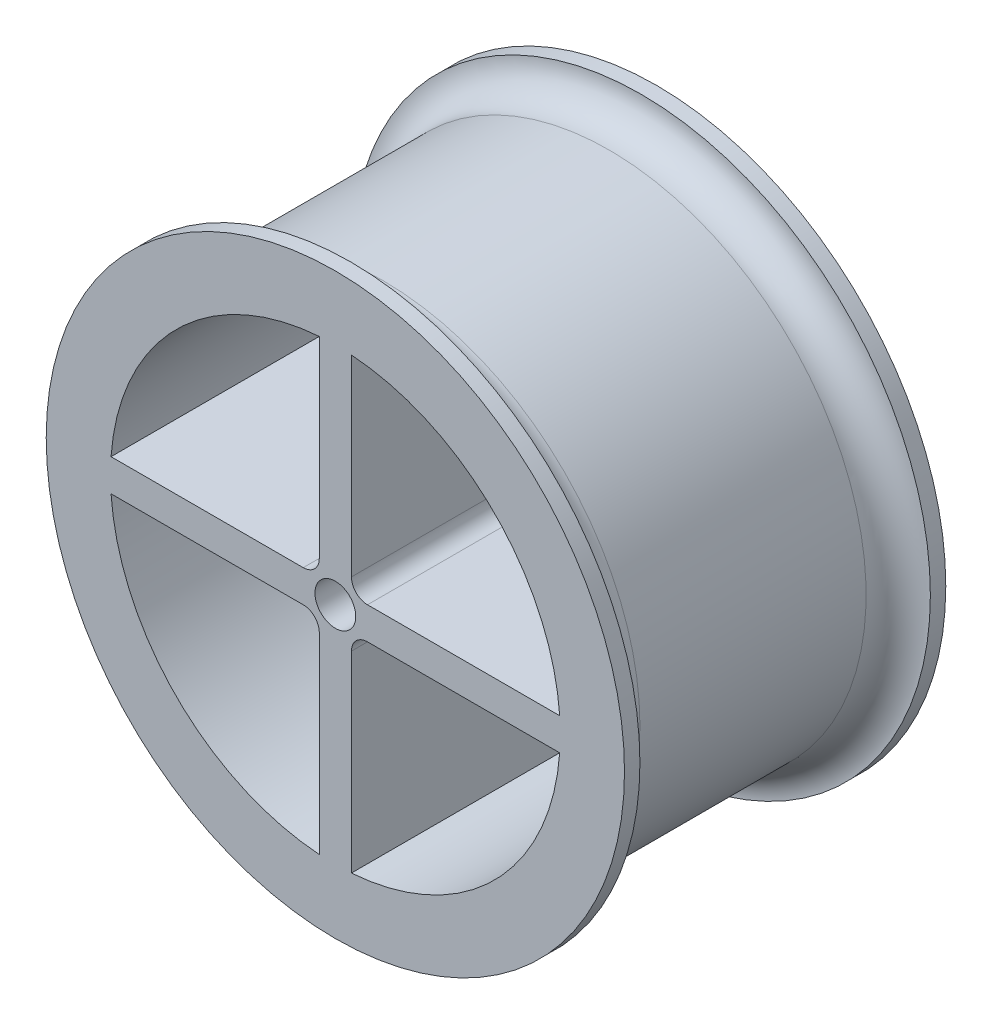
SolidWorks part; units mm, degrees
ref_plane "Front Plane" through (0, 0, 0) normal (0, 0, 1) x (1, 0, 0)
ref_plane "Top Plane" through (0, 0, 0) normal (0, 1, 0) x (1, 0, 0)
ref_plane "Right Plane" through (0, 0, 0) normal (1, 0, 0) x (0, 0, -1)
sketch "Sketch1" plane through (0, 0, 0) normal (0, 0, 1) x (1, 0, 0)
  line L1 (-2.5, 39.9218) -> (2.5, 39.9218)
  line L2 (-2.5, 39.9218) -> (-2.5, -39.9218)
  line L3 (-2.5, -39.9218) -> (2.5, -39.9218)
  line L4 (2.5, 39.9218) -> (2.5, -39.9218)
  line L5 (-2.5, 39.9218) -> (2.5, -39.9218) construction
  line L6 (-2.5, -39.9218) -> (2.5, 39.9218) construction
  line L7 (-39.9218, 2.5) -> (39.9218, 2.5)
  line L8 (-39.9218, 2.5) -> (-39.9218, -2.5)
  line L9 (-39.9218, -2.5) -> (39.9218, -2.5)
  line L10 (39.9218, 2.5) -> (39.9218, -2.5)
  line L11 (-39.9218, 2.5) -> (39.9218, -2.5) construction
  line L12 (-39.9218, -2.5) -> (39.9218, 2.5) construction
  circle A0 centre (0, 0) radius 3.175
  circle A1 centre (0, 0) radius 40
  circle A3 centre (0, 0) radius 35
  dimension "D1" = 6.35
  dimension "D2" = 80
  dimension "D6" = 70
  dimension "D3" = 5
  dimension "D4" = 5
extrude "Boss-Extrude6" add sketch "Sketch1" along normal mid plane 50 contours A3 L9 A1 L2 | A3 L2 A1 L7 | A3 L7 L8 L9 | L7 A3 L9 L2 A0 | A3 L4 L1 L2 | L4 A3 L2 L7 A0 | A3 L7 A1 L4 | A3 L9 L10 L7 | A3 L4 A1 L9 | L9 A3 L7 L4 A0 | L2 A3 L4 L9 A0 | A3 L2 L3 L4 | L8 A1 | L3 A1 | L10 A1 | L1 A1 | A0 L7 L2 | A0 L4 L7 | A0 L9 L4 | A0 L2 L9 region at (0, 39.9531, 0) region at (0, 37.4459, 0) region at (-3.0292, 37.4162, 0) region at (27.9101, 27.9101, 0) region at (0, 18.9144, 0) region at (-37.4459, 0, 0) region at (-39.9531, 0, 0) region at (37.4459, 0, 0) region at (39.9531, 0, 0) region at (-2.3265, 2.3265, 0) region at (-18.9144, 0, 0) region at (-37.4162, -3.0292, 0) region at (18.9144, 0, 0) region at (2.3265, 2.3265, 0) region at (27.9101, -27.9101, 0) region at (0, -37.4459, 0) region at (0, -39.9531, 0) region at (-2.3265, -2.3265, 0) region at (0, -18.9144, 0) region at (2.3265, -2.3265, 0)
sketch "Sketch2" plane through (0, 0, 25) normal (0, 0, 1) x (1, 0, 0)
  circle A0 centre (0, 0) radius 40 construction
  circle A1 centre (0, 0) radius 40
  circle A2 centre (0, 0) radius 45
  dimension "D1" = 5
extrude "Boss-Extrude7" add sketch "Sketch2" against normal blind 2.4
fillet "Fillet1" radius 2.5 4 edges at (-2.5, -2.5, 0) (2.5, -2.5, 0) (2.5, 2.5, 0) (-2.5, 2.5, 0)
fillet "Fillet2" radius 5 1 edges at (40, 0, 22.6)
mirror "Mirror1" about plane through (0, 0, 0) normal (0, 0, 1) of "Boss-Extrude7", "Fillet2"
